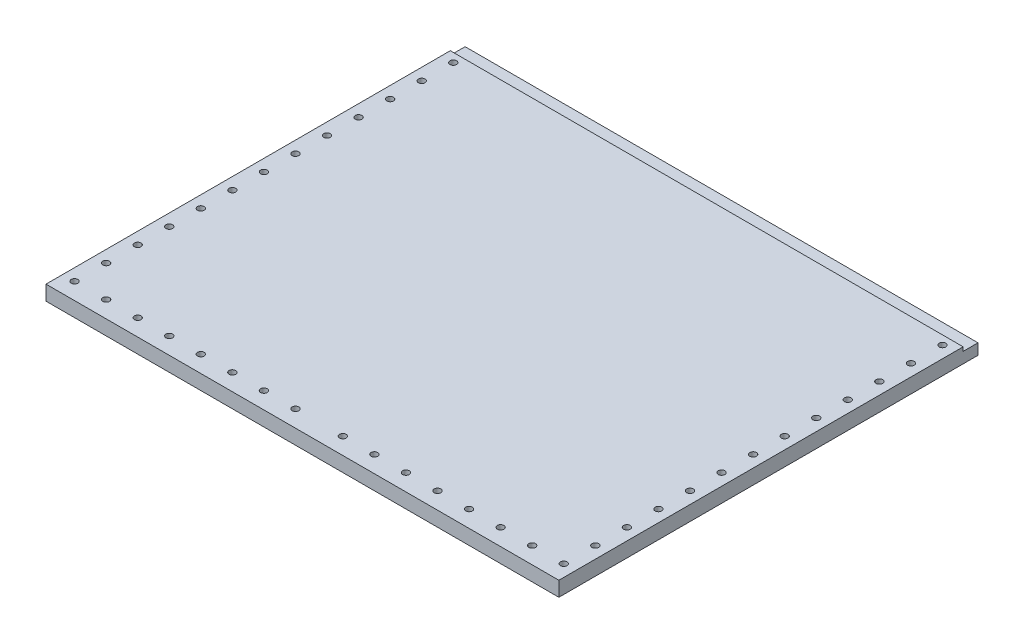
SolidWorks part; units mm, degrees
material "Ductile Iron"
ref_plane "Front Plane" through (0, 0, 0) normal (0, 0, 1) x (1, 0, 0)
ref_plane "Top Plane" through (0, 0, 0) normal (0, 1, 0) x (1, 0, 0)
ref_plane "Right Plane" through (0, 0, 0) normal (1, 0, 0) x (0, 0, -1)
sketch "Sketch1" plane through (0, 0, 0) normal (0, 1, 0) x (1, 0, 0)
  line L1 (0, 0) -> (412.75, 0)
  line L2 (0, 0) -> (0, 584.2)
  line L3 (0, 584.2) -> (412.75, 584.2)
  line L4 (412.75, 0) -> (412.75, 584.2)
  dimension "D1" = 584.2
  dimension "D2" = 412.75
extrude "Boss-Extrude1" add sketch "Sketch1" along normal blind 11.9062
sketch "Sketch2" plane through (0, 11.9062, 0) normal (0, 1, 0) x (1, 0, 0)
  line L0 (0, 584.2) -> (0, 0) construction
  line L1 (0, 477.012) -> (40.64, 477.012)
  line L2 (0, 477.012) -> (0, 337.312)
  line L3 (0, 337.312) -> (40.64, 337.312)
  line L4 (40.64, 477.012) -> (40.64, 337.312)
  line L5 (206.375, 0) -> (206.375, 59.5989)
  line L7 (0, 0) -> (412.75, 0) construction
  line L8 (372.11, 477.012) -> (372.11, 337.312)
  line L9 (412.75, 337.312) -> (372.11, 337.312)
  line L10 (412.75, 477.012) -> (412.75, 337.312)
  line L11 (412.75, 477.012) -> (372.11, 477.012)
  line M5 (0, 584.2) -> (0, 0)
  line M7 (412.75, 0) -> (412.75, 584.2)
  dimension "D1" = 139.7
  dimension "D2" = 40.64
extrude "Cut-Extrude1" cut sketch "Sketch2" against normal through all contours L4 L1 L3 M5 | L11 L8 L9 M7 region at (20.32, 11.9062, -407.162) region at (392.43, 11.9062, -407.162)
sketch "Sketch3" plane through (0, 11.9062, 0) normal (0, 1, 0) x (1, 0, 0)
  line L0 (0, 337.312) -> (0, 0) construction
  line L1 (0, 0) -> (412.75, 0) construction
  circle A0 centre (9.525, 13.462) radius 2.667
  circle A2 centre (34.925, 13.462) radius 2.667
  circle A4 centre (60.325, 13.462) radius 2.667
  circle A6 centre (85.725, 13.462) radius 2.667
  circle A8 centre (111.125, 13.462) radius 2.667
  circle A10 centre (136.525, 13.462) radius 2.667
  circle A12 centre (161.925, 13.462) radius 2.667
  circle A14 centre (187.325, 13.462) radius 2.667
  circle A17 centre (225.425, 13.462) radius 2.667
  circle A19 centre (250.825, 13.462) radius 2.667
  circle A21 centre (276.225, 13.462) radius 2.667
  circle A23 centre (301.625, 13.462) radius 2.667
  circle A25 centre (327.025, 13.462) radius 2.667
  circle A27 centre (352.425, 13.462) radius 2.667
  circle A29 centre (377.825, 13.462) radius 2.667
  circle A31 centre (403.225, 13.462) radius 2.667
  circle A62 centre (403.225, 38.862) radius 2.667
  circle A93 centre (403.225, 64.262) radius 2.667
  circle A124 centre (403.225, 89.662) radius 2.667
  circle A155 centre (403.225, 115.062) radius 2.667
  circle A186 centre (403.225, 140.462) radius 2.667
  circle A217 centre (403.225, 165.862) radius 2.667
  circle A248 centre (403.225, 191.262) radius 2.667
  circle A279 centre (403.225, 216.662) radius 2.667
  circle A310 centre (403.225, 242.062) radius 2.667
  circle A341 centre (403.225, 267.462) radius 2.667
  circle A372 centre (403.225, 292.862) radius 2.667
  circle A403 centre (403.225, 318.262) radius 2.667
  circle A434 centre (403.225, 343.662) radius 2.667
  circle A465 centre (403.225, 369.062) radius 2.667
  circle A496 centre (403.225, 394.462) radius 2.667
  circle A527 centre (403.225, 419.862) radius 2.667
  circle A558 centre (403.225, 445.262) radius 2.667
  circle A589 centre (403.225, 470.662) radius 2.667
  circle A620 centre (403.225, 496.062) radius 2.667
  circle A651 centre (403.225, 521.462) radius 2.667
  circle A682 centre (403.225, 546.862) radius 2.667
  circle A713 centre (403.225, 572.262) radius 2.667
  circle A714 centre (9.525, 38.862) radius 2.667
  circle A715 centre (9.525, 64.262) radius 2.667
  circle A716 centre (9.525, 89.662) radius 2.667
  circle A717 centre (9.525, 115.062) radius 2.667
  circle A718 centre (9.525, 140.462) radius 2.667
  circle A719 centre (9.525, 165.862) radius 2.667
  circle A720 centre (9.525, 191.262) radius 2.667
  circle A721 centre (9.525, 216.662) radius 2.667
  circle A722 centre (9.525, 242.062) radius 2.667
  circle A723 centre (9.525, 267.462) radius 2.667
  circle A724 centre (9.525, 292.862) radius 2.667
  circle A725 centre (9.525, 318.262) radius 2.667
  circle A726 centre (9.525, 343.662) radius 2.667
  circle A727 centre (9.525, 369.062) radius 2.667
  circle A728 centre (9.525, 394.462) radius 2.667
  circle A729 centre (9.525, 419.862) radius 2.667
  circle A730 centre (9.525, 445.262) radius 2.667
  circle A731 centre (9.525, 470.662) radius 2.667
  circle A732 centre (9.525, 496.062) radius 2.667
  circle A733 centre (9.525, 521.462) radius 2.667
  circle A734 centre (9.525, 546.862) radius 2.667
  circle A735 centre (9.525, 572.262) radius 2.667
  circle A736 centre (34.925, 38.862) radius 2.667 [skipped]
  circle A737 centre (47.625, 38.862) radius 2.667 [skipped]
  circle A738 centre (60.325, 38.862) radius 2.667 [skipped]
  circle A739 centre (73.025, 38.862) radius 2.667 [skipped]
  circle A740 centre (85.725, 38.862) radius 2.667 [skipped]
  circle A741 centre (98.425, 38.862) radius 2.667 [skipped]
  circle A742 centre (111.125, 38.862) radius 2.667 [skipped]
  circle A743 centre (123.825, 38.862) radius 2.667 [skipped]
  circle A744 centre (136.525, 38.862) radius 2.667 [skipped]
  circle A745 centre (149.225, 38.862) radius 2.667 [skipped]
  circle A746 centre (161.925, 38.862) radius 2.667 [skipped]
  circle A747 centre (174.625, 38.862) radius 2.667 [skipped]
  circle A748 centre (187.325, 38.862) radius 2.667 [skipped]
  circle A749 centre (200.025, 38.862) radius 2.667 [skipped]
  circle A750 centre (212.725, 38.862) radius 2.667 [skipped]
  circle A751 centre (225.425, 38.862) radius 2.667 [skipped]
  circle A752 centre (238.125, 38.862) radius 2.667 [skipped]
  circle A753 centre (250.825, 38.862) radius 2.667 [skipped]
  circle A754 centre (263.525, 38.862) radius 2.667 [skipped]
  circle A755 centre (276.225, 38.862) radius 2.667 [skipped]
  circle A756 centre (288.925, 38.862) radius 2.667 [skipped]
  circle A757 centre (301.625, 38.862) radius 2.667 [skipped]
  circle A758 centre (314.325, 38.862) radius 2.667 [skipped]
  circle A759 centre (327.025, 38.862) radius 2.667 [skipped]
  circle A760 centre (339.725, 38.862) radius 2.667 [skipped]
  circle A761 centre (352.425, 38.862) radius 2.667 [skipped]
  circle A762 centre (365.125, 38.862) radius 2.667 [skipped]
  circle A763 centre (377.825, 38.862) radius 2.667 [skipped]
  circle A764 centre (390.525, 38.862) radius 2.667 [skipped]
  circle A765 centre (34.925, 64.262) radius 2.667 [skipped]
  circle A766 centre (47.625, 64.262) radius 2.667 [skipped]
  circle A767 centre (60.325, 64.262) radius 2.667 [skipped]
  circle A768 centre (73.025, 64.262) radius 2.667 [skipped]
  circle A769 centre (85.725, 64.262) radius 2.667 [skipped]
  circle A770 centre (98.425, 64.262) radius 2.667 [skipped]
  circle A771 centre (111.125, 64.262) radius 2.667 [skipped]
  circle A772 centre (123.825, 64.262) radius 2.667 [skipped]
  circle A773 centre (136.525, 64.262) radius 2.667 [skipped]
  circle A774 centre (149.225, 64.262) radius 2.667 [skipped]
  circle A775 centre (161.925, 64.262) radius 2.667 [skipped]
  circle A776 centre (174.625, 64.262) radius 2.667 [skipped]
  circle A777 centre (187.325, 64.262) radius 2.667 [skipped]
  circle A778 centre (200.025, 64.262) radius 2.667 [skipped]
  circle A779 centre (212.725, 64.262) radius 2.667 [skipped]
  circle A780 centre (225.425, 64.262) radius 2.667 [skipped]
  circle A781 centre (238.125, 64.262) radius 2.667 [skipped]
  circle A782 centre (250.825, 64.262) radius 2.667 [skipped]
  circle A783 centre (263.525, 64.262) radius 2.667 [skipped]
  circle A784 centre (276.225, 64.262) radius 2.667 [skipped]
  circle A785 centre (288.925, 64.262) radius 2.667 [skipped]
  circle A786 centre (301.625, 64.262) radius 2.667 [skipped]
  circle A787 centre (314.325, 64.262) radius 2.667 [skipped]
  circle A788 centre (327.025, 64.262) radius 2.667 [skipped]
  circle A789 centre (339.725, 64.262) radius 2.667 [skipped]
  circle A790 centre (352.425, 64.262) radius 2.667 [skipped]
  circle A791 centre (365.125, 64.262) radius 2.667 [skipped]
  circle A792 centre (377.825, 64.262) radius 2.667 [skipped]
  circle A793 centre (390.525, 64.262) radius 2.667 [skipped]
  circle A794 centre (34.925, 89.662) radius 2.667 [skipped]
  circle A795 centre (47.625, 89.662) radius 2.667 [skipped]
  circle A796 centre (60.325, 89.662) radius 2.667 [skipped]
  circle A797 centre (73.025, 89.662) radius 2.667 [skipped]
  circle A798 centre (85.725, 89.662) radius 2.667 [skipped]
  circle A799 centre (98.425, 89.662) radius 2.667 [skipped]
  circle A800 centre (111.125, 89.662) radius 2.667 [skipped]
  circle A801 centre (123.825, 89.662) radius 2.667 [skipped]
  circle A802 centre (136.525, 89.662) radius 2.667 [skipped]
  circle A803 centre (149.225, 89.662) radius 2.667 [skipped]
  circle A804 centre (161.925, 89.662) radius 2.667 [skipped]
  circle A805 centre (174.625, 89.662) radius 2.667 [skipped]
  circle A806 centre (187.325, 89.662) radius 2.667 [skipped]
  circle A807 centre (200.025, 89.662) radius 2.667 [skipped]
  circle A808 centre (212.725, 89.662) radius 2.667 [skipped]
  circle A809 centre (225.425, 89.662) radius 2.667 [skipped]
  circle A810 centre (238.125, 89.662) radius 2.667 [skipped]
  circle A811 centre (250.825, 89.662) radius 2.667 [skipped]
  circle A812 centre (263.525, 89.662) radius 2.667 [skipped]
  circle A813 centre (276.225, 89.662) radius 2.667 [skipped]
  circle A814 centre (288.925, 89.662) radius 2.667 [skipped]
  circle A815 centre (301.625, 89.662) radius 2.667 [skipped]
  circle A816 centre (314.325, 89.662) radius 2.667 [skipped]
  circle A817 centre (327.025, 89.662) radius 2.667 [skipped]
  circle A818 centre (339.725, 89.662) radius 2.667 [skipped]
  circle A819 centre (352.425, 89.662) radius 2.667 [skipped]
  circle A820 centre (365.125, 89.662) radius 2.667 [skipped]
  circle A821 centre (377.825, 89.662) radius 2.667 [skipped]
  circle A822 centre (390.525, 89.662) radius 2.667 [skipped]
  circle A823 centre (34.925, 115.062) radius 2.667 [skipped]
  circle A824 centre (47.625, 115.062) radius 2.667 [skipped]
  circle A825 centre (60.325, 115.062) radius 2.667 [skipped]
  circle A826 centre (73.025, 115.062) radius 2.667 [skipped]
  circle A827 centre (85.725, 115.062) radius 2.667 [skipped]
  circle A828 centre (98.425, 115.062) radius 2.667 [skipped]
  circle A829 centre (111.125, 115.062) radius 2.667 [skipped]
  circle A830 centre (123.825, 115.062) radius 2.667 [skipped]
  circle A831 centre (136.525, 115.062) radius 2.667 [skipped]
  circle A832 centre (149.225, 115.062) radius 2.667 [skipped]
  circle A833 centre (161.925, 115.062) radius 2.667 [skipped]
  circle A834 centre (174.625, 115.062) radius 2.667 [skipped]
  circle A835 centre (187.325, 115.062) radius 2.667 [skipped]
  circle A836 centre (200.025, 115.062) radius 2.667 [skipped]
  circle A837 centre (212.725, 115.062) radius 2.667 [skipped]
  circle A838 centre (225.425, 115.062) radius 2.667 [skipped]
  circle A839 centre (238.125, 115.062) radius 2.667 [skipped]
  circle A840 centre (250.825, 115.062) radius 2.667 [skipped]
  circle A841 centre (263.525, 115.062) radius 2.667 [skipped]
  circle A842 centre (276.225, 115.062) radius 2.667 [skipped]
  circle A843 centre (288.925, 115.062) radius 2.667 [skipped]
  circle A844 centre (301.625, 115.062) radius 2.667 [skipped]
  circle A845 centre (314.325, 115.062) radius 2.667 [skipped]
  circle A846 centre (327.025, 115.062) radius 2.667 [skipped]
  circle A847 centre (339.725, 115.062) radius 2.667 [skipped]
  circle A848 centre (352.425, 115.062) radius 2.667 [skipped]
  circle A849 centre (365.125, 115.062) radius 2.667 [skipped]
  circle A850 centre (377.825, 115.062) radius 2.667 [skipped]
  circle A851 centre (390.525, 115.062) radius 2.667 [skipped]
  circle A852 centre (34.925, 140.462) radius 2.667 [skipped]
  circle A853 centre (47.625, 140.462) radius 2.667 [skipped]
  circle A854 centre (60.325, 140.462) radius 2.667 [skipped]
  circle A855 centre (73.025, 140.462) radius 2.667 [skipped]
  circle A856 centre (85.725, 140.462) radius 2.667 [skipped]
  circle A857 centre (98.425, 140.462) radius 2.667 [skipped]
  circle A858 centre (111.125, 140.462) radius 2.667 [skipped]
  circle A859 centre (123.825, 140.462) radius 2.667 [skipped]
  circle A860 centre (136.525, 140.462) radius 2.667 [skipped]
  circle A861 centre (149.225, 140.462) radius 2.667 [skipped]
  circle A862 centre (161.925, 140.462) radius 2.667 [skipped]
  circle A863 centre (174.625, 140.462) radius 2.667 [skipped]
  circle A864 centre (187.325, 140.462) radius 2.667 [skipped]
  circle A865 centre (200.025, 140.462) radius 2.667 [skipped]
  circle A866 centre (212.725, 140.462) radius 2.667 [skipped]
  circle A867 centre (225.425, 140.462) radius 2.667 [skipped]
  circle A868 centre (238.125, 140.462) radius 2.667 [skipped]
  circle A869 centre (250.825, 140.462) radius 2.667 [skipped]
  circle A870 centre (263.525, 140.462) radius 2.667 [skipped]
  circle A871 centre (276.225, 140.462) radius 2.667 [skipped]
  circle A872 centre (288.925, 140.462) radius 2.667 [skipped]
  circle A873 centre (301.625, 140.462) radius 2.667 [skipped]
  circle A874 centre (314.325, 140.462) radius 2.667 [skipped]
  circle A875 centre (327.025, 140.462) radius 2.667 [skipped]
  circle A876 centre (339.725, 140.462) radius 2.667 [skipped]
  circle A877 centre (352.425, 140.462) radius 2.667 [skipped]
  circle A878 centre (365.125, 140.462) radius 2.667 [skipped]
  circle A879 centre (377.825, 140.462) radius 2.667 [skipped]
  circle A880 centre (390.525, 140.462) radius 2.667 [skipped]
  circle A881 centre (34.925, 165.862) radius 2.667 [skipped]
  circle A882 centre (47.625, 165.862) radius 2.667 [skipped]
  circle A883 centre (60.325, 165.862) radius 2.667 [skipped]
  circle A884 centre (73.025, 165.862) radius 2.667 [skipped]
  circle A885 centre (85.725, 165.862) radius 2.667 [skipped]
  circle A886 centre (98.425, 165.862) radius 2.667 [skipped]
  circle A887 centre (111.125, 165.862) radius 2.667 [skipped]
  circle A888 centre (123.825, 165.862) radius 2.667 [skipped]
  circle A889 centre (136.525, 165.862) radius 2.667 [skipped]
  circle A890 centre (149.225, 165.862) radius 2.667 [skipped]
  circle A891 centre (161.925, 165.862) radius 2.667 [skipped]
  circle A892 centre (174.625, 165.862) radius 2.667 [skipped]
  circle A893 centre (187.325, 165.862) radius 2.667 [skipped]
  circle A894 centre (200.025, 165.862) radius 2.667 [skipped]
  circle A895 centre (212.725, 165.862) radius 2.667 [skipped]
  circle A896 centre (225.425, 165.862) radius 2.667 [skipped]
  circle A897 centre (238.125, 165.862) radius 2.667 [skipped]
  circle A898 centre (250.825, 165.862) radius 2.667 [skipped]
  circle A899 centre (263.525, 165.862) radius 2.667 [skipped]
  circle A900 centre (276.225, 165.862) radius 2.667 [skipped]
  circle A901 centre (288.925, 165.862) radius 2.667 [skipped]
  circle A902 centre (301.625, 165.862) radius 2.667 [skipped]
  circle A903 centre (314.325, 165.862) radius 2.667 [skipped]
  circle A904 centre (327.025, 165.862) radius 2.667 [skipped]
  circle A905 centre (339.725, 165.862) radius 2.667 [skipped]
  circle A906 centre (352.425, 165.862) radius 2.667 [skipped]
  circle A907 centre (365.125, 165.862) radius 2.667 [skipped]
  circle A908 centre (377.825, 165.862) radius 2.667 [skipped]
  circle A909 centre (390.525, 165.862) radius 2.667 [skipped]
  circle A910 centre (34.925, 191.262) radius 2.667 [skipped]
  circle A911 centre (47.625, 191.262) radius 2.667 [skipped]
  circle A912 centre (60.325, 191.262) radius 2.667 [skipped]
  circle A913 centre (73.025, 191.262) radius 2.667 [skipped]
  circle A914 centre (85.725, 191.262) radius 2.667 [skipped]
  circle A915 centre (98.425, 191.262) radius 2.667 [skipped]
  circle A916 centre (111.125, 191.262) radius 2.667 [skipped]
  circle A917 centre (123.825, 191.262) radius 2.667 [skipped]
  circle A918 centre (136.525, 191.262) radius 2.667 [skipped]
  circle A919 centre (149.225, 191.262) radius 2.667 [skipped]
  circle A920 centre (161.925, 191.262) radius 2.667 [skipped]
  circle A921 centre (174.625, 191.262) radius 2.667 [skipped]
  circle A922 centre (187.325, 191.262) radius 2.667 [skipped]
  circle A923 centre (200.025, 191.262) radius 2.667 [skipped]
  circle A924 centre (212.725, 191.262) radius 2.667 [skipped]
  circle A925 centre (225.425, 191.262) radius 2.667 [skipped]
  circle A926 centre (238.125, 191.262) radius 2.667 [skipped]
  circle A927 centre (250.825, 191.262) radius 2.667 [skipped]
  circle A928 centre (263.525, 191.262) radius 2.667 [skipped]
  circle A929 centre (276.225, 191.262) radius 2.667 [skipped]
  circle A930 centre (288.925, 191.262) radius 2.667 [skipped]
  circle A931 centre (301.625, 191.262) radius 2.667 [skipped]
  circle A932 centre (314.325, 191.262) radius 2.667 [skipped]
  circle A933 centre (327.025, 191.262) radius 2.667 [skipped]
  circle A934 centre (339.725, 191.262) radius 2.667 [skipped]
  circle A935 centre (352.425, 191.262) radius 2.667 [skipped]
  circle A936 centre (365.125, 191.262) radius 2.667 [skipped]
  circle A937 centre (377.825, 191.262) radius 2.667 [skipped]
  circle A938 centre (390.525, 191.262) radius 2.667 [skipped]
  circle A939 centre (34.925, 216.662) radius 2.667 [skipped]
  circle A940 centre (47.625, 216.662) radius 2.667 [skipped]
  circle A941 centre (60.325, 216.662) radius 2.667 [skipped]
  circle A942 centre (73.025, 216.662) radius 2.667 [skipped]
  circle A943 centre (85.725, 216.662) radius 2.667 [skipped]
  circle A944 centre (98.425, 216.662) radius 2.667 [skipped]
  circle A945 centre (111.125, 216.662) radius 2.667 [skipped]
  circle A946 centre (123.825, 216.662) radius 2.667 [skipped]
  circle A947 centre (136.525, 216.662) radius 2.667 [skipped]
  circle A948 centre (149.225, 216.662) radius 2.667 [skipped]
  circle A949 centre (161.925, 216.662) radius 2.667 [skipped]
  circle A950 centre (174.625, 216.662) radius 2.667 [skipped]
  circle A951 centre (187.325, 216.662) radius 2.667 [skipped]
  circle A952 centre (200.025, 216.662) radius 2.667 [skipped]
  circle A953 centre (212.725, 216.662) radius 2.667 [skipped]
  circle A954 centre (225.425, 216.662) radius 2.667 [skipped]
  circle A955 centre (238.125, 216.662) radius 2.667 [skipped]
  circle A956 centre (250.825, 216.662) radius 2.667 [skipped]
  circle A957 centre (263.525, 216.662) radius 2.667 [skipped]
  circle A958 centre (276.225, 216.662) radius 2.667 [skipped]
  circle A959 centre (288.925, 216.662) radius 2.667 [skipped]
  circle A960 centre (301.625, 216.662) radius 2.667 [skipped]
  circle A961 centre (314.325, 216.662) radius 2.667 [skipped]
  circle A962 centre (327.025, 216.662) radius 2.667 [skipped]
  circle A963 centre (339.725, 216.662) radius 2.667 [skipped]
  circle A964 centre (352.425, 216.662) radius 2.667 [skipped]
  circle A965 centre (365.125, 216.662) radius 2.667 [skipped]
  circle A966 centre (377.825, 216.662) radius 2.667 [skipped]
  circle A967 centre (390.525, 216.662) radius 2.667 [skipped]
  circle A968 centre (34.925, 242.062) radius 2.667 [skipped]
  circle A969 centre (47.625, 242.062) radius 2.667 [skipped]
  circle A970 centre (60.325, 242.062) radius 2.667 [skipped]
  circle A971 centre (73.025, 242.062) radius 2.667 [skipped]
  circle A972 centre (85.725, 242.062) radius 2.667 [skipped]
  circle A973 centre (98.425, 242.062) radius 2.667 [skipped]
  circle A974 centre (111.125, 242.062) radius 2.667 [skipped]
  circle A975 centre (123.825, 242.062) radius 2.667 [skipped]
  circle A976 centre (136.525, 242.062) radius 2.667 [skipped]
  circle A977 centre (149.225, 242.062) radius 2.667 [skipped]
  circle A978 centre (161.925, 242.062) radius 2.667 [skipped]
  circle A979 centre (174.625, 242.062) radius 2.667 [skipped]
  circle A980 centre (187.325, 242.062) radius 2.667 [skipped]
  circle A981 centre (200.025, 242.062) radius 2.667 [skipped]
  circle A982 centre (212.725, 242.062) radius 2.667 [skipped]
  circle A983 centre (225.425, 242.062) radius 2.667 [skipped]
  circle A984 centre (238.125, 242.062) radius 2.667 [skipped]
  circle A985 centre (250.825, 242.062) radius 2.667 [skipped]
  circle A986 centre (263.525, 242.062) radius 2.667 [skipped]
  circle A987 centre (276.225, 242.062) radius 2.667 [skipped]
  circle A988 centre (288.925, 242.062) radius 2.667 [skipped]
  circle A989 centre (301.625, 242.062) radius 2.667 [skipped]
  circle A990 centre (314.325, 242.062) radius 2.667 [skipped]
  circle A991 centre (327.025, 242.062) radius 2.667 [skipped]
  circle A992 centre (339.725, 242.062) radius 2.667 [skipped]
  circle A993 centre (352.425, 242.062) radius 2.667 [skipped]
  circle A994 centre (365.125, 242.062) radius 2.667 [skipped]
  circle A995 centre (377.825, 242.062) radius 2.667 [skipped]
  circle A996 centre (390.525, 242.062) radius 2.667 [skipped]
  circle A997 centre (34.925, 267.462) radius 2.667 [skipped]
  circle A998 centre (47.625, 267.462) radius 2.667 [skipped]
  circle A999 centre (60.325, 267.462) radius 2.667 [skipped]
  circle A1000 centre (73.025, 267.462) radius 2.667 [skipped]
  circle A1001 centre (85.725, 267.462) radius 2.667 [skipped]
  circle A1002 centre (98.425, 267.462) radius 2.667 [skipped]
  circle A1003 centre (111.125, 267.462) radius 2.667 [skipped]
  circle A1004 centre (123.825, 267.462) radius 2.667 [skipped]
  circle A1005 centre (136.525, 267.462) radius 2.667 [skipped]
  circle A1006 centre (149.225, 267.462) radius 2.667 [skipped]
  circle A1007 centre (161.925, 267.462) radius 2.667 [skipped]
  circle A1008 centre (174.625, 267.462) radius 2.667 [skipped]
  circle A1009 centre (187.325, 267.462) radius 2.667 [skipped]
  circle A1010 centre (200.025, 267.462) radius 2.667 [skipped]
  circle A1011 centre (212.725, 267.462) radius 2.667 [skipped]
  circle A1012 centre (225.425, 267.462) radius 2.667 [skipped]
  circle A1013 centre (238.125, 267.462) radius 2.667 [skipped]
  circle A1014 centre (250.825, 267.462) radius 2.667 [skipped]
  circle A1015 centre (263.525, 267.462) radius 2.667 [skipped]
  circle A1016 centre (276.225, 267.462) radius 2.667 [skipped]
  circle A1017 centre (288.925, 267.462) radius 2.667 [skipped]
  circle A1018 centre (301.625, 267.462) radius 2.667 [skipped]
  circle A1019 centre (314.325, 267.462) radius 2.667 [skipped]
  circle A1020 centre (327.025, 267.462) radius 2.667 [skipped]
  circle A1021 centre (339.725, 267.462) radius 2.667 [skipped]
  circle A1022 centre (352.425, 267.462) radius 2.667 [skipped]
  circle A1023 centre (365.125, 267.462) radius 2.667 [skipped]
  circle A1024 centre (377.825, 267.462) radius 2.667 [skipped]
  circle A1025 centre (390.525, 267.462) radius 2.667 [skipped]
  circle A1026 centre (34.925, 292.862) radius 2.667 [skipped]
  circle A1027 centre (47.625, 292.862) radius 2.667 [skipped]
  circle A1028 centre (60.325, 292.862) radius 2.667 [skipped]
  circle A1029 centre (73.025, 292.862) radius 2.667 [skipped]
  circle A1030 centre (85.725, 292.862) radius 2.667 [skipped]
  circle A1031 centre (98.425, 292.862) radius 2.667 [skipped]
  circle A1032 centre (111.125, 292.862) radius 2.667 [skipped]
  circle A1033 centre (123.825, 292.862) radius 2.667 [skipped]
  circle A1034 centre (136.525, 292.862) radius 2.667 [skipped]
  circle A1035 centre (149.225, 292.862) radius 2.667 [skipped]
  circle A1036 centre (161.925, 292.862) radius 2.667 [skipped]
  circle A1037 centre (174.625, 292.862) radius 2.667 [skipped]
  circle A1038 centre (187.325, 292.862) radius 2.667 [skipped]
  circle A1039 centre (200.025, 292.862) radius 2.667 [skipped]
  circle A1040 centre (212.725, 292.862) radius 2.667 [skipped]
  circle A1041 centre (225.425, 292.862) radius 2.667 [skipped]
  circle A1042 centre (238.125, 292.862) radius 2.667 [skipped]
  circle A1043 centre (250.825, 292.862) radius 2.667 [skipped]
  circle A1044 centre (263.525, 292.862) radius 2.667 [skipped]
  circle A1045 centre (276.225, 292.862) radius 2.667 [skipped]
  circle A1046 centre (288.925, 292.862) radius 2.667 [skipped]
  circle A1047 centre (301.625, 292.862) radius 2.667 [skipped]
  circle A1048 centre (314.325, 292.862) radius 2.667 [skipped]
  circle A1049 centre (327.025, 292.862) radius 2.667 [skipped]
  circle A1050 centre (339.725, 292.862) radius 2.667 [skipped]
  circle A1051 centre (352.425, 292.862) radius 2.667 [skipped]
  circle A1052 centre (365.125, 292.862) radius 2.667 [skipped]
  circle A1053 centre (377.825, 292.862) radius 2.667 [skipped]
  circle A1054 centre (390.525, 292.862) radius 2.667 [skipped]
  circle A1055 centre (34.925, 318.262) radius 2.667 [skipped]
  circle A1056 centre (47.625, 318.262) radius 2.667 [skipped]
  circle A1057 centre (60.325, 318.262) radius 2.667 [skipped]
  circle A1058 centre (73.025, 318.262) radius 2.667 [skipped]
  circle A1059 centre (85.725, 318.262) radius 2.667 [skipped]
  circle A1060 centre (98.425, 318.262) radius 2.667 [skipped]
  circle A1061 centre (111.125, 318.262) radius 2.667 [skipped]
  circle A1062 centre (123.825, 318.262) radius 2.667 [skipped]
  circle A1063 centre (136.525, 318.262) radius 2.667 [skipped]
  circle A1064 centre (149.225, 318.262) radius 2.667 [skipped]
  circle A1065 centre (161.925, 318.262) radius 2.667 [skipped]
  circle A1066 centre (174.625, 318.262) radius 2.667 [skipped]
  circle A1067 centre (187.325, 318.262) radius 2.667 [skipped]
  circle A1068 centre (200.025, 318.262) radius 2.667 [skipped]
  circle A1069 centre (212.725, 318.262) radius 2.667 [skipped]
  circle A1070 centre (225.425, 318.262) radius 2.667 [skipped]
  circle A1071 centre (238.125, 318.262) radius 2.667 [skipped]
  circle A1072 centre (250.825, 318.262) radius 2.667 [skipped]
  circle A1073 centre (263.525, 318.262) radius 2.667 [skipped]
  circle A1074 centre (276.225, 318.262) radius 2.667 [skipped]
  circle A1075 centre (288.925, 318.262) radius 2.667 [skipped]
  circle A1076 centre (301.625, 318.262) radius 2.667 [skipped]
  circle A1077 centre (314.325, 318.262) radius 2.667 [skipped]
  circle A1078 centre (327.025, 318.262) radius 2.667 [skipped]
  circle A1079 centre (339.725, 318.262) radius 2.667 [skipped]
  circle A1080 centre (352.425, 318.262) radius 2.667 [skipped]
  circle A1081 centre (365.125, 318.262) radius 2.667 [skipped]
  circle A1082 centre (377.825, 318.262) radius 2.667 [skipped]
  circle A1083 centre (390.525, 318.262) radius 2.667 [skipped]
  circle A1084 centre (34.925, 343.662) radius 2.667 [skipped]
  circle A1085 centre (47.625, 343.662) radius 2.667 [skipped]
  circle A1086 centre (60.325, 343.662) radius 2.667 [skipped]
  circle A1087 centre (73.025, 343.662) radius 2.667 [skipped]
  circle A1088 centre (85.725, 343.662) radius 2.667 [skipped]
  circle A1089 centre (98.425, 343.662) radius 2.667 [skipped]
  circle A1090 centre (111.125, 343.662) radius 2.667 [skipped]
  circle A1091 centre (123.825, 343.662) radius 2.667 [skipped]
  circle A1092 centre (136.525, 343.662) radius 2.667 [skipped]
  circle A1093 centre (149.225, 343.662) radius 2.667 [skipped]
  circle A1094 centre (161.925, 343.662) radius 2.667 [skipped]
  circle A1095 centre (174.625, 343.662) radius 2.667 [skipped]
  circle A1096 centre (187.325, 343.662) radius 2.667 [skipped]
  circle A1097 centre (200.025, 343.662) radius 2.667 [skipped]
  circle A1098 centre (212.725, 343.662) radius 2.667 [skipped]
  circle A1099 centre (225.425, 343.662) radius 2.667 [skipped]
  circle A1100 centre (238.125, 343.662) radius 2.667 [skipped]
  circle A1101 centre (250.825, 343.662) radius 2.667 [skipped]
  circle A1102 centre (263.525, 343.662) radius 2.667 [skipped]
  circle A1103 centre (276.225, 343.662) radius 2.667 [skipped]
  circle A1104 centre (288.925, 343.662) radius 2.667 [skipped]
  circle A1105 centre (301.625, 343.662) radius 2.667 [skipped]
  circle A1106 centre (314.325, 343.662) radius 2.667 [skipped]
  circle A1107 centre (327.025, 343.662) radius 2.667 [skipped]
  circle A1108 centre (339.725, 343.662) radius 2.667 [skipped]
  circle A1109 centre (352.425, 343.662) radius 2.667 [skipped]
  circle A1110 centre (365.125, 343.662) radius 2.667 [skipped]
  circle A1111 centre (377.825, 343.662) radius 2.667 [skipped]
  circle A1112 centre (390.525, 343.662) radius 2.667 [skipped]
  circle A1113 centre (34.925, 369.062) radius 2.667 [skipped]
  circle A1114 centre (47.625, 369.062) radius 2.667 [skipped]
  circle A1115 centre (60.325, 369.062) radius 2.667 [skipped]
  circle A1116 centre (73.025, 369.062) radius 2.667 [skipped]
  circle A1117 centre (85.725, 369.062) radius 2.667 [skipped]
  circle A1118 centre (98.425, 369.062) radius 2.667 [skipped]
  circle A1119 centre (111.125, 369.062) radius 2.667 [skipped]
  circle A1120 centre (123.825, 369.062) radius 2.667 [skipped]
  circle A1121 centre (136.525, 369.062) radius 2.667 [skipped]
  circle A1122 centre (149.225, 369.062) radius 2.667 [skipped]
  circle A1123 centre (161.925, 369.062) radius 2.667 [skipped]
  circle A1124 centre (174.625, 369.062) radius 2.667 [skipped]
  circle A1125 centre (187.325, 369.062) radius 2.667 [skipped]
  circle A1126 centre (200.025, 369.062) radius 2.667 [skipped]
  circle A1127 centre (212.725, 369.062) radius 2.667 [skipped]
  circle A1128 centre (225.425, 369.062) radius 2.667 [skipped]
  circle A1129 centre (238.125, 369.062) radius 2.667 [skipped]
  circle A1130 centre (250.825, 369.062) radius 2.667 [skipped]
  circle A1131 centre (263.525, 369.062) radius 2.667 [skipped]
  circle A1132 centre (276.225, 369.062) radius 2.667 [skipped]
  circle A1133 centre (288.925, 369.062) radius 2.667 [skipped]
  circle A1134 centre (301.625, 369.062) radius 2.667 [skipped]
  circle A1135 centre (314.325, 369.062) radius 2.667 [skipped]
  circle A1136 centre (327.025, 369.062) radius 2.667 [skipped]
  circle A1137 centre (339.725, 369.062) radius 2.667 [skipped]
  circle A1138 centre (352.425, 369.062) radius 2.667 [skipped]
  circle A1139 centre (365.125, 369.062) radius 2.667 [skipped]
  circle A1140 centre (377.825, 369.062) radius 2.667 [skipped]
  circle A1141 centre (390.525, 369.062) radius 2.667 [skipped]
  circle A1142 centre (34.925, 394.462) radius 2.667 [skipped]
  circle A1143 centre (47.625, 394.462) radius 2.667 [skipped]
  circle A1144 centre (60.325, 394.462) radius 2.667 [skipped]
  circle A1145 centre (73.025, 394.462) radius 2.667 [skipped]
  circle A1146 centre (85.725, 394.462) radius 2.667 [skipped]
  circle A1147 centre (98.425, 394.462) radius 2.667 [skipped]
  circle A1148 centre (111.125, 394.462) radius 2.667 [skipped]
  circle A1149 centre (123.825, 394.462) radius 2.667 [skipped]
  circle A1150 centre (136.525, 394.462) radius 2.667 [skipped]
  circle A1151 centre (149.225, 394.462) radius 2.667 [skipped]
  circle A1152 centre (161.925, 394.462) radius 2.667 [skipped]
  circle A1153 centre (174.625, 394.462) radius 2.667 [skipped]
  circle A1154 centre (187.325, 394.462) radius 2.667 [skipped]
  circle A1155 centre (200.025, 394.462) radius 2.667 [skipped]
  circle A1156 centre (212.725, 394.462) radius 2.667 [skipped]
  circle A1157 centre (225.425, 394.462) radius 2.667 [skipped]
  circle A1158 centre (238.125, 394.462) radius 2.667 [skipped]
  circle A1159 centre (250.825, 394.462) radius 2.667 [skipped]
  circle A1160 centre (263.525, 394.462) radius 2.667 [skipped]
  circle A1161 centre (276.225, 394.462) radius 2.667 [skipped]
  circle A1162 centre (288.925, 394.462) radius 2.667 [skipped]
  circle A1163 centre (301.625, 394.462) radius 2.667 [skipped]
  circle A1164 centre (314.325, 394.462) radius 2.667 [skipped]
  circle A1165 centre (327.025, 394.462) radius 2.667 [skipped]
  circle A1166 centre (339.725, 394.462) radius 2.667 [skipped]
  circle A1167 centre (352.425, 394.462) radius 2.667 [skipped]
  circle A1168 centre (365.125, 394.462) radius 2.667 [skipped]
  circle A1169 centre (377.825, 394.462) radius 2.667 [skipped]
  circle A1170 centre (390.525, 394.462) radius 2.667 [skipped]
  circle A1171 centre (34.925, 419.862) radius 2.667 [skipped]
  circle A1172 centre (47.625, 419.862) radius 2.667 [skipped]
  circle A1173 centre (60.325, 419.862) radius 2.667 [skipped]
  circle A1174 centre (73.025, 419.862) radius 2.667 [skipped]
  circle A1175 centre (85.725, 419.862) radius 2.667 [skipped]
  circle A1176 centre (98.425, 419.862) radius 2.667 [skipped]
  circle A1177 centre (111.125, 419.862) radius 2.667 [skipped]
  circle A1178 centre (123.825, 419.862) radius 2.667 [skipped]
  circle A1179 centre (136.525, 419.862) radius 2.667 [skipped]
  circle A1180 centre (149.225, 419.862) radius 2.667 [skipped]
  circle A1181 centre (161.925, 419.862) radius 2.667 [skipped]
  circle A1182 centre (174.625, 419.862) radius 2.667 [skipped]
  circle A1183 centre (187.325, 419.862) radius 2.667 [skipped]
  circle A1184 centre (200.025, 419.862) radius 2.667 [skipped]
  circle A1185 centre (212.725, 419.862) radius 2.667 [skipped]
  circle A1186 centre (225.425, 419.862) radius 2.667 [skipped]
  circle A1187 centre (238.125, 419.862) radius 2.667 [skipped]
  circle A1188 centre (250.825, 419.862) radius 2.667 [skipped]
  circle A1189 centre (263.525, 419.862) radius 2.667 [skipped]
  circle A1190 centre (276.225, 419.862) radius 2.667 [skipped]
  circle A1191 centre (288.925, 419.862) radius 2.667 [skipped]
  circle A1192 centre (301.625, 419.862) radius 2.667 [skipped]
  circle A1193 centre (314.325, 419.862) radius 2.667 [skipped]
  circle A1194 centre (327.025, 419.862) radius 2.667 [skipped]
  circle A1195 centre (339.725, 419.862) radius 2.667 [skipped]
  circle A1196 centre (352.425, 419.862) radius 2.667 [skipped]
  circle A1197 centre (365.125, 419.862) radius 2.667 [skipped]
  circle A1198 centre (377.825, 419.862) radius 2.667 [skipped]
  circle A1199 centre (390.525, 419.862) radius 2.667 [skipped]
  circle A1200 centre (34.925, 445.262) radius 2.667 [skipped]
  circle A1201 centre (47.625, 445.262) radius 2.667 [skipped]
  circle A1202 centre (60.325, 445.262) radius 2.667 [skipped]
  circle A1203 centre (73.025, 445.262) radius 2.667 [skipped]
  circle A1204 centre (85.725, 445.262) radius 2.667 [skipped]
  circle A1205 centre (98.425, 445.262) radius 2.667 [skipped]
  circle A1206 centre (111.125, 445.262) radius 2.667 [skipped]
  circle A1207 centre (123.825, 445.262) radius 2.667 [skipped]
  circle A1208 centre (136.525, 445.262) radius 2.667 [skipped]
  circle A1209 centre (149.225, 445.262) radius 2.667 [skipped]
  circle A1210 centre (161.925, 445.262) radius 2.667 [skipped]
  circle A1211 centre (174.625, 445.262) radius 2.667 [skipped]
  circle A1212 centre (187.325, 445.262) radius 2.667 [skipped]
  circle A1213 centre (200.025, 445.262) radius 2.667 [skipped]
  circle A1214 centre (212.725, 445.262) radius 2.667 [skipped]
  circle A1215 centre (225.425, 445.262) radius 2.667 [skipped]
  circle A1216 centre (238.125, 445.262) radius 2.667 [skipped]
  circle A1217 centre (250.825, 445.262) radius 2.667 [skipped]
  circle A1218 centre (263.525, 445.262) radius 2.667 [skipped]
  circle A1219 centre (276.225, 445.262) radius 2.667 [skipped]
  circle A1220 centre (288.925, 445.262) radius 2.667 [skipped]
  circle A1221 centre (301.625, 445.262) radius 2.667 [skipped]
  circle A1222 centre (314.325, 445.262) radius 2.667 [skipped]
  circle A1223 centre (327.025, 445.262) radius 2.667 [skipped]
  circle A1224 centre (339.725, 445.262) radius 2.667 [skipped]
  circle A1225 centre (352.425, 445.262) radius 2.667 [skipped]
  circle A1226 centre (365.125, 445.262) radius 2.667 [skipped]
  circle A1227 centre (377.825, 445.262) radius 2.667 [skipped]
  circle A1228 centre (390.525, 445.262) radius 2.667 [skipped]
  circle A1229 centre (34.925, 470.662) radius 2.667 [skipped]
  circle A1230 centre (47.625, 470.662) radius 2.667 [skipped]
  circle A1231 centre (60.325, 470.662) radius 2.667 [skipped]
  circle A1232 centre (73.025, 470.662) radius 2.667 [skipped]
  circle A1233 centre (85.725, 470.662) radius 2.667 [skipped]
  circle A1234 centre (98.425, 470.662) radius 2.667 [skipped]
  circle A1235 centre (111.125, 470.662) radius 2.667 [skipped]
  circle A1236 centre (123.825, 470.662) radius 2.667 [skipped]
  circle A1237 centre (136.525, 470.662) radius 2.667 [skipped]
  circle A1238 centre (149.225, 470.662) radius 2.667 [skipped]
  circle A1239 centre (161.925, 470.662) radius 2.667 [skipped]
  circle A1240 centre (174.625, 470.662) radius 2.667 [skipped]
  circle A1241 centre (187.325, 470.662) radius 2.667 [skipped]
  circle A1242 centre (200.025, 470.662) radius 2.667 [skipped]
  circle A1243 centre (212.725, 470.662) radius 2.667 [skipped]
  circle A1244 centre (225.425, 470.662) radius 2.667 [skipped]
  circle A1245 centre (238.125, 470.662) radius 2.667 [skipped]
  circle A1246 centre (250.825, 470.662) radius 2.667 [skipped]
  circle A1247 centre (263.525, 470.662) radius 2.667 [skipped]
  circle A1248 centre (276.225, 470.662) radius 2.667 [skipped]
  circle A1249 centre (288.925, 470.662) radius 2.667 [skipped]
  circle A1250 centre (301.625, 470.662) radius 2.667 [skipped]
  circle A1251 centre (314.325, 470.662) radius 2.667 [skipped]
  circle A1252 centre (327.025, 470.662) radius 2.667 [skipped]
  circle A1253 centre (339.725, 470.662) radius 2.667 [skipped]
  circle A1254 centre (352.425, 470.662) radius 2.667 [skipped]
  circle A1255 centre (365.125, 470.662) radius 2.667 [skipped]
  circle A1256 centre (377.825, 470.662) radius 2.667 [skipped]
  circle A1257 centre (390.525, 470.662) radius 2.667 [skipped]
  circle A1258 centre (34.925, 496.062) radius 2.667 [skipped]
  circle A1259 centre (47.625, 496.062) radius 2.667 [skipped]
  circle A1260 centre (60.325, 496.062) radius 2.667 [skipped]
  circle A1261 centre (73.025, 496.062) radius 2.667 [skipped]
  circle A1262 centre (85.725, 496.062) radius 2.667 [skipped]
  circle A1263 centre (98.425, 496.062) radius 2.667 [skipped]
  circle A1264 centre (111.125, 496.062) radius 2.667 [skipped]
  circle A1265 centre (123.825, 496.062) radius 2.667 [skipped]
  circle A1266 centre (136.525, 496.062) radius 2.667 [skipped]
  circle A1267 centre (149.225, 496.062) radius 2.667 [skipped]
  circle A1268 centre (161.925, 496.062) radius 2.667 [skipped]
  circle A1269 centre (174.625, 496.062) radius 2.667 [skipped]
  circle A1270 centre (187.325, 496.062) radius 2.667 [skipped]
  circle A1271 centre (200.025, 496.062) radius 2.667 [skipped]
  circle A1272 centre (212.725, 496.062) radius 2.667 [skipped]
  circle A1273 centre (225.425, 496.062) radius 2.667 [skipped]
  circle A1274 centre (238.125, 496.062) radius 2.667 [skipped]
  circle A1275 centre (250.825, 496.062) radius 2.667 [skipped]
  circle A1276 centre (263.525, 496.062) radius 2.667 [skipped]
  circle A1277 centre (276.225, 496.062) radius 2.667 [skipped]
  circle A1278 centre (288.925, 496.062) radius 2.667 [skipped]
  circle A1279 centre (301.625, 496.062) radius 2.667 [skipped]
  circle A1280 centre (314.325, 496.062) radius 2.667 [skipped]
  circle A1281 centre (327.025, 496.062) radius 2.667 [skipped]
  circle A1282 centre (339.725, 496.062) radius 2.667 [skipped]
  circle A1283 centre (352.425, 496.062) radius 2.667 [skipped]
  circle A1284 centre (365.125, 496.062) radius 2.667 [skipped]
  circle A1285 centre (377.825, 496.062) radius 2.667 [skipped]
  circle A1286 centre (390.525, 496.062) radius 2.667 [skipped]
  circle A1287 centre (34.925, 521.462) radius 2.667 [skipped]
  circle A1288 centre (47.625, 521.462) radius 2.667 [skipped]
  circle A1289 centre (60.325, 521.462) radius 2.667 [skipped]
  circle A1290 centre (73.025, 521.462) radius 2.667 [skipped]
  circle A1291 centre (85.725, 521.462) radius 2.667 [skipped]
  circle A1292 centre (98.425, 521.462) radius 2.667 [skipped]
  circle A1293 centre (111.125, 521.462) radius 2.667 [skipped]
  circle A1294 centre (123.825, 521.462) radius 2.667 [skipped]
  circle A1295 centre (136.525, 521.462) radius 2.667 [skipped]
  circle A1296 centre (149.225, 521.462) radius 2.667 [skipped]
  circle A1297 centre (161.925, 521.462) radius 2.667 [skipped]
  circle A1298 centre (174.625, 521.462) radius 2.667 [skipped]
  circle A1299 centre (187.325, 521.462) radius 2.667 [skipped]
  circle A1300 centre (200.025, 521.462) radius 2.667 [skipped]
  circle A1301 centre (212.725, 521.462) radius 2.667 [skipped]
  circle A1302 centre (225.425, 521.462) radius 2.667 [skipped]
  circle A1303 centre (238.125, 521.462) radius 2.667 [skipped]
  circle A1304 centre (250.825, 521.462) radius 2.667 [skipped]
  circle A1305 centre (263.525, 521.462) radius 2.667 [skipped]
  circle A1306 centre (276.225, 521.462) radius 2.667 [skipped]
  circle A1307 centre (288.925, 521.462) radius 2.667 [skipped]
  circle A1308 centre (301.625, 521.462) radius 2.667 [skipped]
  circle A1309 centre (314.325, 521.462) radius 2.667 [skipped]
  circle A1310 centre (327.025, 521.462) radius 2.667 [skipped]
  circle A1311 centre (339.725, 521.462) radius 2.667 [skipped]
  circle A1312 centre (352.425, 521.462) radius 2.667 [skipped]
  circle A1313 centre (365.125, 521.462) radius 2.667 [skipped]
  circle A1314 centre (377.825, 521.462) radius 2.667 [skipped]
  circle A1315 centre (390.525, 521.462) radius 2.667 [skipped]
  circle A1316 centre (34.925, 546.862) radius 2.667 [skipped]
  circle A1317 centre (47.625, 546.862) radius 2.667 [skipped]
  circle A1318 centre (60.325, 546.862) radius 2.667 [skipped]
  circle A1319 centre (73.025, 546.862) radius 2.667 [skipped]
  circle A1320 centre (85.725, 546.862) radius 2.667 [skipped]
  circle A1321 centre (98.425, 546.862) radius 2.667 [skipped]
  circle A1322 centre (111.125, 546.862) radius 2.667 [skipped]
  circle A1323 centre (123.825, 546.862) radius 2.667 [skipped]
  circle A1324 centre (136.525, 546.862) radius 2.667 [skipped]
  circle A1325 centre (149.225, 546.862) radius 2.667 [skipped]
  circle A1326 centre (161.925, 546.862) radius 2.667 [skipped]
  circle A1327 centre (174.625, 546.862) radius 2.667 [skipped]
  circle A1328 centre (187.325, 546.862) radius 2.667 [skipped]
  circle A1329 centre (200.025, 546.862) radius 2.667 [skipped]
  circle A1330 centre (212.725, 546.862) radius 2.667 [skipped]
  circle A1331 centre (225.425, 546.862) radius 2.667 [skipped]
  circle A1332 centre (238.125, 546.862) radius 2.667 [skipped]
  circle A1333 centre (250.825, 546.862) radius 2.667 [skipped]
  circle A1334 centre (263.525, 546.862) radius 2.667 [skipped]
  circle A1335 centre (276.225, 546.862) radius 2.667 [skipped]
  circle A1336 centre (288.925, 546.862) radius 2.667 [skipped]
  circle A1337 centre (301.625, 546.862) radius 2.667 [skipped]
  circle A1338 centre (314.325, 546.862) radius 2.667 [skipped]
  circle A1339 centre (327.025, 546.862) radius 2.667 [skipped]
  circle A1340 centre (339.725, 546.862) radius 2.667 [skipped]
  circle A1341 centre (352.425, 546.862) radius 2.667 [skipped]
  circle A1342 centre (365.125, 546.862) radius 2.667 [skipped]
  circle A1343 centre (377.825, 546.862) radius 2.667 [skipped]
  circle A1344 centre (390.525, 546.862) radius 2.667 [skipped]
  circle A1345 centre (34.925, 572.262) radius 2.667 [skipped]
  circle A1346 centre (47.625, 572.262) radius 2.667 [skipped]
  circle A1347 centre (60.325, 572.262) radius 2.667 [skipped]
  circle A1348 centre (73.025, 572.262) radius 2.667 [skipped]
  circle A1349 centre (85.725, 572.262) radius 2.667 [skipped]
  circle A1350 centre (98.425, 572.262) radius 2.667 [skipped]
  circle A1351 centre (111.125, 572.262) radius 2.667 [skipped]
  circle A1352 centre (123.825, 572.262) radius 2.667 [skipped]
  circle A1353 centre (136.525, 572.262) radius 2.667 [skipped]
  circle A1354 centre (149.225, 572.262) radius 2.667 [skipped]
  circle A1355 centre (161.925, 572.262) radius 2.667 [skipped]
  circle A1356 centre (174.625, 572.262) radius 2.667 [skipped]
  circle A1357 centre (187.325, 572.262) radius 2.667 [skipped]
  circle A1358 centre (200.025, 572.262) radius 2.667 [skipped]
  circle A1359 centre (212.725, 572.262) radius 2.667 [skipped]
  circle A1360 centre (225.425, 572.262) radius 2.667 [skipped]
  circle A1361 centre (238.125, 572.262) radius 2.667 [skipped]
  circle A1362 centre (250.825, 572.262) radius 2.667 [skipped]
  circle A1363 centre (263.525, 572.262) radius 2.667 [skipped]
  circle A1364 centre (276.225, 572.262) radius 2.667 [skipped]
  circle A1365 centre (288.925, 572.262) radius 2.667 [skipped]
  circle A1366 centre (301.625, 572.262) radius 2.667 [skipped]
  circle A1367 centre (314.325, 572.262) radius 2.667 [skipped]
  circle A1368 centre (327.025, 572.262) radius 2.667 [skipped]
  circle A1369 centre (339.725, 572.262) radius 2.667 [skipped]
  circle A1370 centre (352.425, 572.262) radius 2.667 [skipped]
  circle A1371 centre (365.125, 572.262) radius 2.667 [skipped]
  circle A1372 centre (377.825, 572.262) radius 2.667 [skipped]
  circle A1373 centre (390.525, 572.262) radius 2.667 [skipped]
  circle A1374 centre (22.225, 38.862) radius 2.667 [skipped]
  circle A1375 centre (22.225, 64.262) radius 2.667 [skipped]
  circle A1376 centre (22.225, 89.662) radius 2.667 [skipped]
  circle A1377 centre (22.225, 115.062) radius 2.667 [skipped]
  circle A1378 centre (22.225, 140.462) radius 2.667 [skipped]
  circle A1379 centre (22.225, 165.862) radius 2.667 [skipped]
  circle A1380 centre (22.225, 191.262) radius 2.667 [skipped]
  circle A1381 centre (22.225, 216.662) radius 2.667 [skipped]
  circle A1382 centre (22.225, 242.062) radius 2.667 [skipped]
  circle A1383 centre (22.225, 267.462) radius 2.667 [skipped]
  circle A1384 centre (22.225, 292.862) radius 2.667 [skipped]
  circle A1385 centre (22.225, 318.262) radius 2.667 [skipped]
  circle A1386 centre (22.225, 343.662) radius 2.667 [skipped]
  circle A1387 centre (22.225, 369.062) radius 2.667 [skipped]
  circle A1388 centre (22.225, 394.462) radius 2.667 [skipped]
  circle A1389 centre (22.225, 419.862) radius 2.667 [skipped]
  circle A1390 centre (22.225, 445.262) radius 2.667 [skipped]
  circle A1391 centre (22.225, 470.662) radius 2.667 [skipped]
  circle A1392 centre (22.225, 496.062) radius 2.667 [skipped]
  circle A1393 centre (22.225, 521.462) radius 2.667 [skipped]
  circle A1394 centre (22.225, 546.862) radius 2.667 [skipped]
  circle A1395 centre (22.225, 572.262) radius 2.667 [skipped]
  circle A1396 centre (22.225, 13.462) radius 2.667 [skipped]
  circle A1397 centre (47.625, 13.462) radius 2.667 [skipped]
  circle A1398 centre (73.025, 13.462) radius 2.667 [skipped]
  circle A1399 centre (98.425, 13.462) radius 2.667 [skipped]
  circle A1400 centre (123.825, 13.462) radius 2.667 [skipped]
  circle A1401 centre (149.225, 13.462) radius 2.667 [skipped]
  circle A1402 centre (390.525, 13.462) radius 2.667 [skipped]
  circle A1403 centre (365.125, 13.462) radius 2.667 [skipped]
  circle A1404 centre (339.725, 13.462) radius 2.667 [skipped]
  circle A1405 centre (314.325, 13.462) radius 2.667 [skipped]
  circle A1406 centre (288.925, 13.462) radius 2.667 [skipped]
  circle A1407 centre (263.525, 13.462) radius 2.667 [skipped]
  circle A1408 centre (174.625, 13.462) radius 2.667 [skipped]
  circle A1409 centre (238.125, 13.462) radius 2.667 [skipped]
  circle A1410 centre (212.725, 13.462) radius 2.667 [skipped]
  circle A1411 centre (200.025, 13.462) radius 2.667 [skipped]
  dimension "D3" = 5.334
  dimension "D1" = 9.525
  dimension "D2" = 13.462
  dimension "D4" = 32
  dimension "D5" = 23
extrude "Cut-Extrude2" cut sketch "Sketch3" against normal blind 254
sketch "Sketch4" plane through (0, 11.9062, 0) normal (0, 1, 0) x (1, 0, 0)
  line L1 (0, 584.2) -> (412.75, 584.2)
  line L2 (0, 584.2) -> (0, 337.312)
  line L3 (0, 337.312) -> (412.75, 337.312)
  line L4 (412.75, 584.2) -> (412.75, 337.312)
extrude "Cut-Extrude4" cut sketch "Sketch4" against normal through all
sketch "Sketch5" plane through (412.75, 0, 0) normal (1, 0, 0) x (0, 0, -1)
  line L1 (337.312, 11.9062) -> (325.374, 11.9062)
  line L2 (337.312, 11.9062) -> (337.312, 8.7312)
  line L3 (337.312, 8.7312) -> (325.374, 8.7312)
  line L4 (325.374, 11.9062) -> (325.374, 8.7312)
  dimension "D1" = 11.938
  dimension "D2" = 3.175
extrude "Cut-Extrude5" cut sketch "Sketch5" against normal through all
